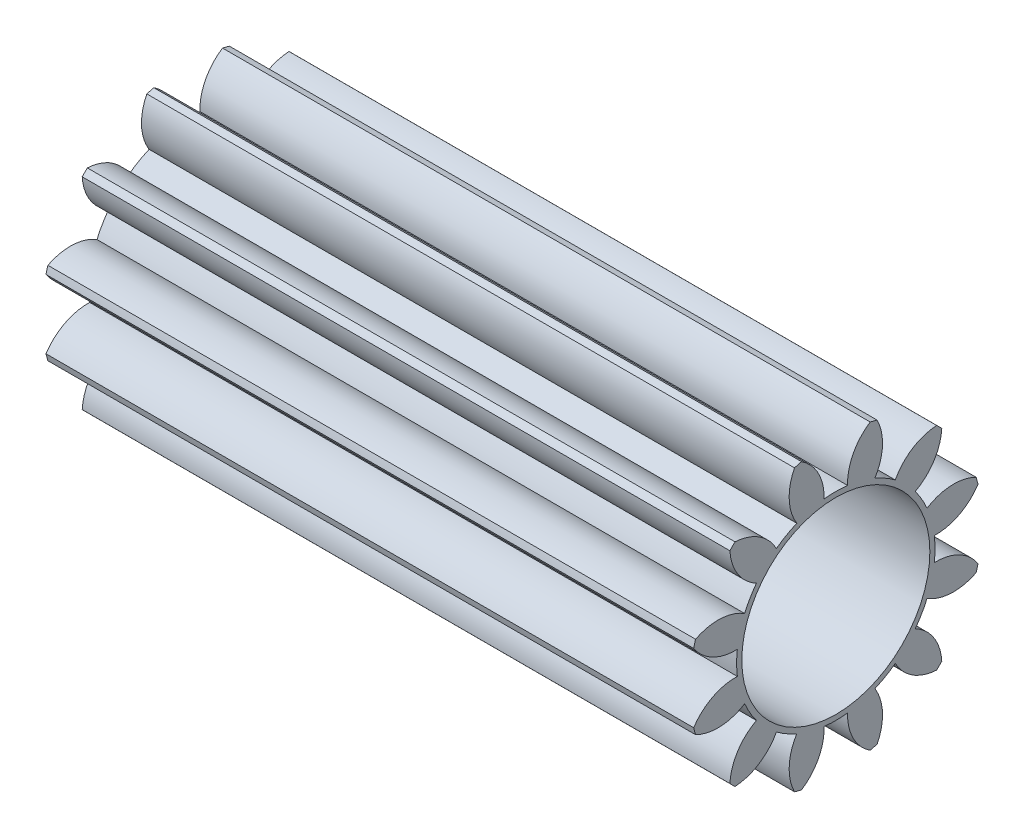
SolidWorks part; units mm, degrees
ref_plane "Plane1" through (0, 0, 0) normal (0, 0, 1) x (1, 0, 0)
ref_plane "Plane2" through (0, 0, 0) normal (0, 1, 0) x (1, 0, 0)
ref_plane "Plane3" through (0, 0, 0) normal (1, 0, 0) x (0, 0, -1)
sketch "HoldingSke" plane through (0, 0, 0) normal (0, 1, 0) x (1, 0, 0)
  line L0 (0, 0) -> (1.9563, -0.4158)
  line L1 (-15, 0) -> (100, 0) construction
  line L2 (0, 0) -> (-2.1039, 2.3779)
  line L3 (0, 0) -> (-11.863, 4.5341)
  line L4 (0, 0) -> (8.4473, 1.7955)
  line L5 (0, 0) -> (-46.8476, -17.4728)
  line L6 (0, 0) -> (-12.8489, -8.6692)
  line L7 (-2.1039, 2.3779) -> (8.6586, 51.2059)
  line L8 (-76.2, 54.61) -> (-75.5, 54.61)
  line L9 (-71.009, 38.7566) -> (-53.1078, 45.2721)
  line L10 (-76.2, 71.12) -> (104.1128, 71.12)
  line L11 (0, 0) -> (-15.5, 0)
  line L12 (-76.2, 101.6) -> (-76.181, 101.6)
  line L13 (24.9733, 27.94) -> (52.9518, 28.4284)
  line L14 (24.9733, 27.94) -> (24.9743, 27.94)
  line L15 (24.9733, 27.94) -> (100.4006, 29.5858)
  line L16 (-63.627, -0.5) -> (-12.827, -0.5)
  circle A0 centre (0, 0) radius 2.25
  circle A1 centre (0, 0) radius 2.374
  circle A2 centre (0, 0) radius 37.5
  circle A3 centre (0, 0) radius 2.25
  dimension "Num_teeth" = 12
  dimension "Pitch_radius" = 180.3128
  dimension "Width" = 15.5
  dimension "Thickness" = 15.5
sketch "BasProSke" plane through (0, 0, 0) normal (0, 1, 0) x (1, 0, 0)
  line L0 (-10, 0) -> (60, 0) construction
  line L1 (0, 0) -> (0, 3.5)
  line L2 (0, 0) -> (15.5, 0)
  line L3 (15.5, 0) -> (15.5, 3.5)
  line L4 (15.5, 3.5) -> (0, 3.5)
  dimension "Thickness" = 15.5
  dimension "Diameter" = 7
revolve "Base-Revolve" add sketch "BasProSke" angle 360 about L0
sketch "TooCutSke" plane through (0, 0, 0) normal (1, 0, 0) x (0, 0, -1)
  line L1 (0, 0) -> (0, 107) construction
  line L2 (0, 0) -> (-0.4248, 2.9698) construction
  line L3 (0, 0) -> (-1.5418, 5.7541) construction
  line L4 (-0.4248, 2.9698) -> (-0.7709, 2.877) construction
  arc A0 (0.2811, 2.3573) -> (-0.2811, 2.3573) centre (0, 0) ccw
  arc A1 (0.8514, 3.421) -> (-0.8514, 3.421) centre (0, 0) ccw
  circle A2 centre (0, 0) radius 3 construction
  circle A3 centre (0, 0) radius 2.8191 construction
  arc A4 (-0.2811, 2.3573) -> (-0.8514, 3.421) centre (-1.4804, 2.3991) ccw
  arc A5 (0.8514, 3.421) -> (0.2811, 2.3573) centre (1.4804, 2.3991) ccw
extrude "ToothCut" cut sketch "TooCutSke" along normal through all
fillet "Breaks" [suppressed] radius 0.01 tangent propagation no
fillet "RootFillets" [suppressed] radius 0.126
pattern_circular "TeethCuts" count 12 every 30 about axis through (-10, 0, 0) along (1, 0, 0) of "ToothCut", "RootFillets", "Breaks"
sketch "HubNeaOneSke" plane through (0, 0, 0) normal (-1, 0, 0) x (0, 0, 1)
  circle A0 centre (0, 0) radius 2.374
  dimension "Diameter" = 4.748
extrude "HubNearOne" [suppressed] add sketch "HubNeaOneSke" along normal blind 34.5001
sketch "HubNeaBotSke" plane through (0, 0, 0) normal (-1, 0, 0) x (0, 0, 1)
  circle A0 centre (0, 0) radius 2.374
  dimension "Diameter" = 4.748
extrude "HubNearBoth" [suppressed] add sketch "HubNeaBotSke" along normal blind 17.25
ref_plane "FarPln" through (15.5, 0, 0) normal (1, 0, 0) x (0, 0, -1)
sketch "HubFarSke" plane through (15.5, 0, 0) normal (1, 0, 0) x (0, 0, -1)
  circle A0 centre (0, 0) radius 2.374
  dimension "Diameter" = 4.748
extrude "HubFar" [suppressed] add sketch "HubFarSke" along normal blind 17.25
sketch "BorSke" plane through (0, 0, 0) normal (1, 0, 0) x (0, 0, -1)
  circle A0 centre (0, 0) radius 2.25
  dimension "Diameter" = 4.5
extrude "Bore" cut sketch "BorSke" along normal mid plane 100.0001
sketch "KeySke" plane through (0, 0, 0) normal (1, 0, 0) x (0, 0, -1)
  line L0 (-0.8, 0) -> (-0.8, 2.95)
  line L1 (-0.8, 2.95) -> (0.8, 2.95)
  line L2 (0.8, 2.95) -> (0.8, 0)
  line L3 (0, 0) -> (0, 34) construction
  line L4 (-0.8, 0) -> (0.8, 0)
extrude "Keyway" [suppressed] cut sketch "KeySke" along normal mid plane 100.0001
pattern_circular "Keyway2" [suppressed] count 2 every 90 about axis through (-10, 0, 0) along (1, 0, 0)
equation "' \"Module@HoldingSke\" = 6.35"
equation "' \"Num_teeth@HoldingSke\" = 12"
equation "' \"Ap@HoldingSke\" =  20"
equation "' \"Ap@HoldingSke\" = 20"
equation "' \"Width@HoldingSke\" = 0.5 * 25.4"
equation "' \"Hub_dia@HoldingSke\"= 1 * 25.4"
equation "' \"Hub_dia@HoldingSke\" = 1 * 25.4"
equation "' \"Overall_len@HoldingSke\" = 1.0 * 25.4"
equation "' \"Bore@HoldingSke\" = 0.75 * 25.4"
equation "' \"T_dim@HoldingSke\" = 0.1 * 25.4"
equation "' \"Width@KeySke\" = 0.25 * 25.4"
equation "' \"Show_teeth@HoldingSke\" = 13"
equation "' \"Backlash@HoldingSke\" = 0.009 * 25.4"
equation "' \"Addendum_fac@HoldingSke\" = 1.0"
equation "' \"Dedendum_fac@HoldingSke\" = 1.25"
equation "' \"Dedendum_add@HoldingSke\" = 0.00005 * 25.4"
equation "' \"Clearance_fac@HoldingSke\" = 0.25"
equation "\"Pitch@HoldingSke\" = 1 / \"Module@HoldingSke\""
equation "\"Overcut_dia@TooCutSke\" = (\"Num_teeth@HoldingSke\" + 2 * \"Addendum_fac@HoldingSke\") / \"Pitch@HoldingSke\" + 0.002 * 25.4"
equation "\"Pitch_dia@TooCutSke\" = \"Num_teeth@HoldingSke\" / \"Pitch@HoldingSke\""
equation "\"Base_dia@TooCutSke\" = \"Num_teeth@HoldingSke\" / \"Pitch@HoldingSke\" * cos((\"Ap@HoldingSke\"  * 3.14159265 / 180))"
equation "\"Root_dia@TooCutSke\" = (\"Num_teeth@HoldingSke\" + 2) / \"Pitch@HoldingSke\" - 2 * (\"Addendum_fac@HoldingSke\" + \"Dedendum_fac@HoldingSke\") / \"Pitch@HoldingSke\" - \"Dedendum_add@HoldingSke\" * 2"
equation "\"Half_ang@TooCutSke\" = 180 / \"Num_teeth@HoldingSke\""
equation "\"Half_CT@TooCutSke\" = \"Num_teeth@HoldingSke\" / \"Pitch@HoldingSke\" * sin((3.14159265 / 2 / \"Num_teeth@HoldingSke\")) / 2 - 7 * \"Backlash@HoldingSke\" / 4"
equation "\"Flank_rad@TooCutSke\" = \"Num_teeth@HoldingSke\" / \"Pitch@HoldingSke\" / 5"
equation "\"Radius@RootFillets\" = \"Clearance_fac@HoldingSke\" / \"Pitch@HoldingSke\" + \"Dedendum_add@HoldingSke\""
equation "\"Break_rad@Breaks\" = 0.02 / \"Pitch@HoldingSke\""
equation "\"Thickness@HoldingSke\" = \"Width@HoldingSke\""
equation "\"OAL@HoldingSke\" = \"Thickness@HoldingSke\""
equation "\"MHD@HoldingSke\" = (\"Num_teeth@HoldingSke\" + 2) / \"Pitch@HoldingSke\" - 2 * (\"Addendum_fac@HoldingSke\" + \"Dedendum_fac@HoldingSke\")  / \"Pitch@HoldingSke\" - \"Dedendum_add@HoldingSke\" * 2"
equation "\"MBD@HoldingSke\" = (\"Num_teeth@HoldingSke\" + 2) / \"Pitch@HoldingSke\" - 2 * (\"Addendum_fac@HoldingSke\" + \"Dedendum_fac@HoldingSke\")  / \"Pitch@HoldingSke\" - \"Dedendum_add@HoldingSke\" * 2 - 0.002 * 25.4"
equation "\"MHD@HoldingSke\" = ((sgn( \"MHD@HoldingSke\" - \"Hub_dia@HoldingSke\" )-1)*( \"MHD@HoldingSke\" - \"Hub_dia@HoldingSke\" ))/-2+ \"Hub_dia@HoldingSke\""
equation "\"MBD@HoldingSke\" = ((sgn( \"MBD@HoldingSke\" - \"Bore@HoldingSke\" )-1)*( \"MBD@HoldingSke\" - \"Bore@HoldingSke\" ))/-2+ \"Bore@HoldingSke\""
equation "\"OAL@HoldingSke\" = ((sgn( \"OAL@HoldingSke\" - \"Overall_len@HoldingSke\" )+1)*( \"OAL@HoldingSke\" - \"Overall_len@HoldingSke\" ))/2 + \"Overall_len@HoldingSke\" + 0.000002 * 25.4"
equation "\"Num_teeth@TeethCuts\" = int( \"Show_teeth@HoldingSke\" ) + 1"
equation "\"Num_teeth@TeethCuts\" = ((sgn( \"Num_teeth@TeethCuts\" - \"Num_teeth@HoldingSke\" )-1)*( \"Num_teeth@TeethCuts\" - \"Num_teeth@HoldingSke\" ))/-2+ \"Num_teeth@HoldingSke\""
equation "\"Num_teeth@TeethCuts\" = ((sgn( \"Num_teeth@TeethCuts\" - 2.0)+1)*( \"Num_teeth@TeethCuts\" - 2.0))/2 +2.0"
equation "\"Angle@TeethCuts\" = 360.0 / \"Num_teeth@HoldingSke\""
equation "\"Diameter@BasProSke\" = (\"Num_teeth@HoldingSke\" + 2 * \"Addendum_fac@HoldingSke\") / \"Pitch@HoldingSke\""
equation "\"Thickness@BasProSke\"  = \"Thickness@HoldingSke\""
equation "' \"Fillet_rad@BasProSke\" =  \"Thickness@HoldingSke\" * 0.05"
equation "' \"Fillet_rad@BasProSke\" = \"Thickness@HoldingSke\" * 0.05"
equation "\"MHD@HoldingSke\" = ((sgn( \"MHD@HoldingSke\" - \"Root_dia@TooCutSke\" )-1)*( \"MHD@HoldingSke\" - \"Root_dia@TooCutSke\" ))/-2+ \"Root_dia@TooCutSke\""
equation "\"Diameter@HubNeaOneSke\" = \"MHD@HoldingSke\""
equation "\"Length@HubNearOne\" = \"OAL@HoldingSke\" - \"Thickness@BasProSke\""
equation "\"Diameter@HubNeaBotSke\" = \"MHD@HoldingSke\""
equation "\"Length@HubNearBoth\" = ( \"OAL@HoldingSke\" - \"Thickness@BasProSke\" ) / 2.0"
equation "\"Thickness@FarPln\" = \"Thickness@BasProSke\""
equation "\"Diameter@HubFarSke\" = \"MHD@HoldingSke\""
equation "\"Length@HubFar\" = ( \"OAL@HoldingSke\" - \"Thickness@BasProSke\" ) / 2.0"
equation "\"Diameter@BorSke\" = \"MBD@HoldingSke\""
equation "\"D1@Bore\" = \"OAL@HoldingSke\" * 2.0"
equation "\"D1@Keyway\" = \"OAL@HoldingSke\" * 2.0"
equation "\"Offset@KeySke\" = \"T_dim@HoldingSke\" + \"MBD@HoldingSke\" / 2.0"
